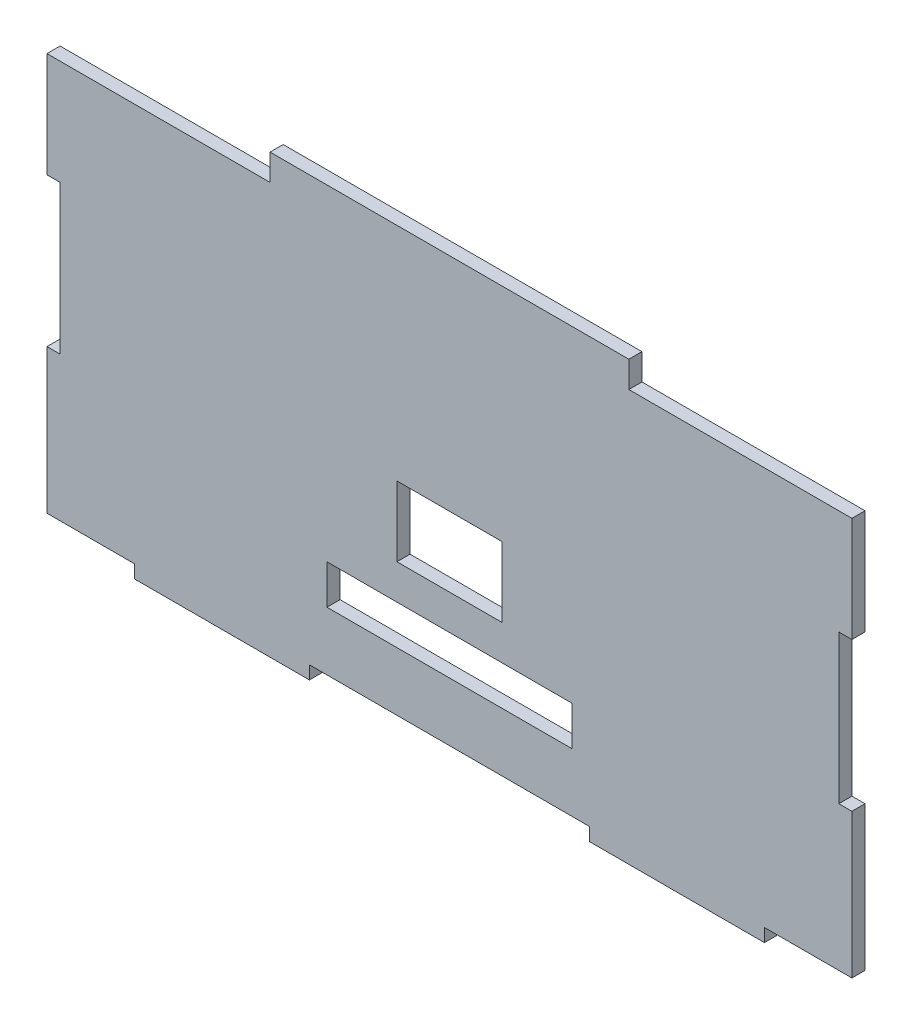
SolidWorks part; units mm, degrees
ref_plane "Front Plane" through (0, 0, 0) normal (0, 0, 1) x (1, 0, 0)
ref_plane "Top Plane" through (0, 0, 0) normal (0, 1, 0) x (1, 0, 0)
ref_plane "Right Plane" through (0, 0, 0) normal (1, 0, 0) x (0, 0, -1)
sketch "Sketch1" plane through (0, 0, 0) normal (0, 0, 1) x (1, 0, 0)
  line L0 (-46, 23.5) -> (-20.5, 23.5)
  line L1 (-46, -23.5) -> (46, -23.5)
  line L2 (-46, -23.5) -> (-46, 23.5)
  line L4 (46, -23.5) -> (46, 23.5)
  line L5 (-46, -23.5) -> (46, 23.5) construction
  line L6 (-46, 23.5) -> (46, -23.5) construction
  line L7 (-20.5, 23.5) -> (-20.5, 26.5)
  line L8 (-20.5, 26.5) -> (20.5, 26.5)
  line L9 (20.5, 26.5) -> (20.5, 23.5)
  line L10 (20.5, 23.5) -> (46, 23.5)
  point P0 (0, 0)
  dimension "D1" = 92
  dimension "D2" = 47
  dimension "D3" = 25.5
  dimension "D4" = 41
  dimension "D5" = 3
  dimension "D6" = 46
extrude "Boss-Extrude1" add sketch "Sketch1" against normal blind 1.5
sketch "Sketch2" plane through (0, 0, 0) normal (0, 0, 1) x (1, 0, 0)
  line L0 (-46, -23.5) -> (46, -23.5) construction
  line L1 (-14, -15.3) -> (14, -15.3)
  line L2 (-14, -15.3) -> (-14, -10.8)
  line L3 (-14, -10.8) -> (14, -10.8)
  line L4 (14, -15.3) -> (14, -10.8)
  line L5 (-14, -15.3) -> (14, -10.8) construction
  line L6 (-14, -10.8) -> (14, -15.3) construction
  line L7 (-46, 23.5) -> (-46, -23.5) construction
  line L8 (46, -23.5) -> (46, 23.5) construction
  line L10 (-6, -6.8) -> (6, -6.8)
  line L11 (-6, -6.8) -> (-6, 1.2)
  line L12 (-6, 1.2) -> (6, 1.2)
  line L13 (6, -6.8) -> (6, 1.2)
  line L14 (-6, -6.8) -> (6, 1.2) construction
  line L15 (-6, 1.2) -> (6, -6.8) construction
  point P0 (0, -13.05)
  point P11 (0, -2.8)
  dimension "D1" = 8.2
  dimension "D2" = 4.5
  dimension "D3" = 32
  dimension "D4" = 32
  dimension "D5" = 4
  dimension "D6" = 8
  dimension "D7" = 40
  dimension "D8" = 40
extrude "Cut-Extrude2" cut sketch "Sketch2" against normal through all
sketch "Sketch3" plane through (0, 0, 0) normal (0, 0, 1) x (1, 0, 0)
  line L0 (-46, 11.5) -> (-44.5, 11.5)
  line L1 (-46, 23.5) -> (-46, -23.5) construction
  line L2 (-44.5, 11.5) -> (-44.5, -5.5)
  line L3 (-44.5, -5.5) -> (-46, -5.5)
  line L4 (-46, -22) -> (-36, -22)
  line L5 (-36, -22) -> (-36, -23.5)
  line L6 (-46, -23.5) -> (46, -23.5) construction
  line L7 (-16, -23.5) -> (-16, -22)
  line L8 (-16, -22) -> (16, -22)
  line L9 (16, -22) -> (16, -23.5)
  line L10 (36, -23.5) -> (36, -22)
  line L11 (36, -22) -> (46, -22)
  line L12 (46, -23.5) -> (46, 23.5) construction
  line L13 (46, 11.5) -> (44.5, 11.5)
  line L14 (44.5, 11.5) -> (44.5, -5.5)
  line L15 (44.5, -5.5) -> (46, -5.5)
  line L16 (-20.5, 23.5) -> (-46, 23.5) construction
  line L17 (-46, 11.5) -> (-46, -5.5)
  line L18 (-36, -23.5) -> (-46, -23.5)
  line L19 (-46, -23.5) -> (-46, -22)
  line L20 (-16, -23.5) -> (16, -23.5)
  line L21 (36, -23.5) -> (46, -23.5)
  line L22 (46, -23.5) -> (46, -22)
  line L23 (46, -5.5) -> (46, 11.5)
  dimension "D1" = 12
  dimension "D2" = 18
  dimension "D3" = 18
  dimension "D4" = 1.5
  dimension "D5" = 1.5
  dimension "D6" = 1.5
  dimension "D7" = 1.5
  dimension "D8" = 1.5
  dimension "D9" = 10
  dimension "D10" = 10
  dimension "D11" = 30
  dimension "D12" = 30
extrude "Cut-Extrude3" cut sketch "Sketch3" against normal through all
